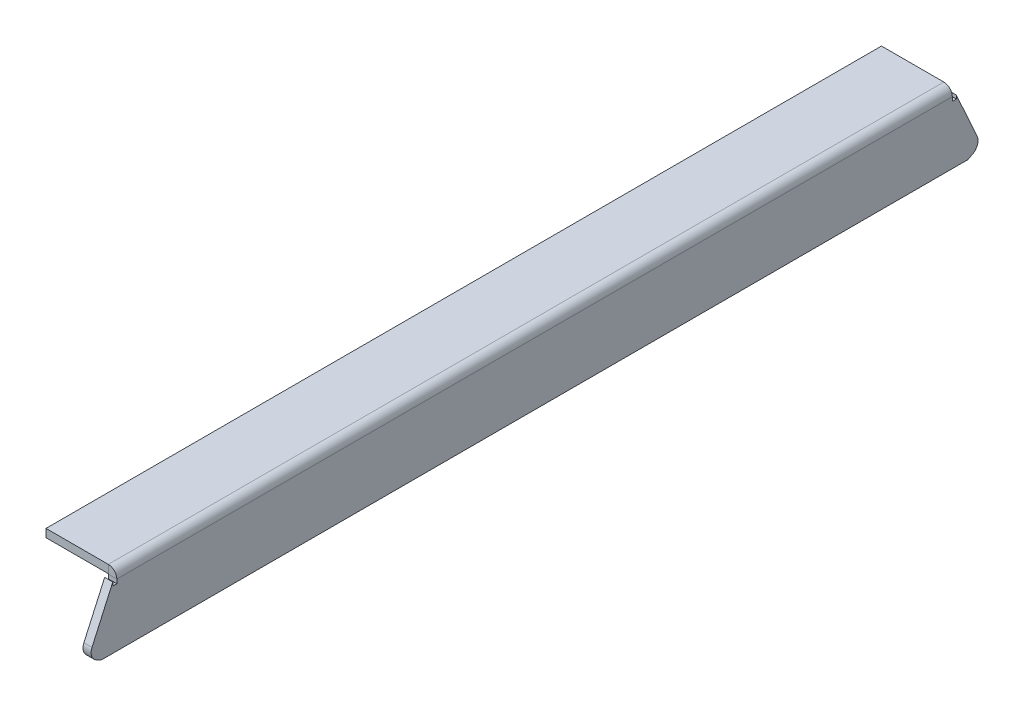
SolidWorks part; units mm, degrees
note: The reader was unsure of these and kept them because the rebuilt part matched: flange length of "Edge-Flange1".
material "ASTM A36 Steel"
ref_plane "Front Plane" through (0, 0, 0) normal (0, 0, 1) x (1, 0, 0)
ref_plane "Top Plane" through (0, 0, 0) normal (0, 1, 0) x (1, 0, 0)
ref_plane "Right Plane" through (0, 0, 0) normal (1, 0, 0) x (0, 0, -1)
sketch "Sketch1" plane through (0, 0, 0) normal (1, 0, 0) x (0, 0, -1)
  line L0 (188.35, 33.3559) -> (-224.592, 33.3559)
  line L1 (196.0009, -1.6441) -> (-232.2429, -1.6441)
  line L2 (-234.5636, -0.4683) -> (-232.2429, -1.6441)
  line L3 (198.3216, -0.4683) -> (196.0009, -1.6441)
  line L4 (-224.592, 33.3559) -> (-236.8647, 6.0411)
  line L5 (188.35, 33.3559) -> (200.6226, 6.0411)
  arc A0 (198.3216, -0.4683) -> (200.6226, 6.0411) centre (196.0619, 3.9919) ccw
  arc A1 (-236.8647, 6.0411) -> (-234.5636, -0.4683) centre (-232.3039, 3.9919) ccw
base flange "Base-Flange1" sketch "Sketch1" thickness 4 reverse thickness direction no parameters "D1"=0.2
edge flange "Edge-Flange1" sketch "Sketch8" flange angle 90 flange length 35 flange position material inside bend radius 0.2 thickness 4 relief rectangular parameters "D6"=10
sketch "Sketch8" plane through (-4, 33.3559, 0) normal (0, -1, 0) x (0, 0, 1)
  line L2 (-188.35, 0) -> (-188.35, 31)
  line L3 (-188.35, 31) -> (224.592, 31)
  line L4 (224.592, 31) -> (224.592, 0)
  line L5 (224.592, 0) -> (-188.35, 0) construction
  line L6 (224.592, 0) -> (-188.35, 0)
bend "EdgeBend1" bend radius 0.2 bend angle 90 parameters "D5"=1
sketch "Bend-Lines1" [suppressed] plane through (0, 0, 0) normal (0, 1, 0) x (1, 0, 0)
sketch "Bounding-Box1" [suppressed] plane through (0, 0, 0) normal (0, 1, 0) x (1, 0, 0)
sheet metal parameters "Sheet-Metal1" thickness 4 parameters "D1"=0.2
flat pattern "Flat-Pattern1" [suppressed]
sketch "Bend-Lines2" plane through (0, 0, 0) normal (0, 1, 0) x (1, 0, 0)
sketch3d "Bounding-Box2" [suppressed]
  line L0 (433.3657, 29.3643, 0) -> (-5, 29.364, 0) construction
  line L1 (433.3657, -5.6356, 0) -> (-5, -5.636, 0) construction
  line L2 (433.3657, 29.3643, 0) -> (433.3657, -5.6356, 0) construction
  line L3 (-5, 29.364, 0) -> (-5, -5.636, 0) construction
sheet metal parameters "Sheet-Metal2" thickness 4 parameters "D1"=0.2
flat pattern "Flat-Pattern1"
sketch "Bend-Lines2" plane through (0, 0, 0) normal (1, 0, 0) x (0, 0, -1)
  line L0 (188.35, 30.8838) -> (-224.592, 30.8838) construction
  line L1 (188.35, 30.8838) -> (-224.592, 30.8838) construction
sketch3d "Bounding-Box2" [suppressed]
  line L0 (-433.3656, 59.4201, 0) -> (5, 59.4197, 0) construction
  line L1 (-433.3657, -5.6356, 0) -> (5, -5.636, 0) construction
  line L2 (-433.3656, 59.4201, 0) -> (-433.3657, -5.6356, 0) construction
  line L3 (5, 59.4197, 0) -> (5, -5.636, 0) construction
bend of the flat pattern "Flatten-<EdgeBend1>1"
